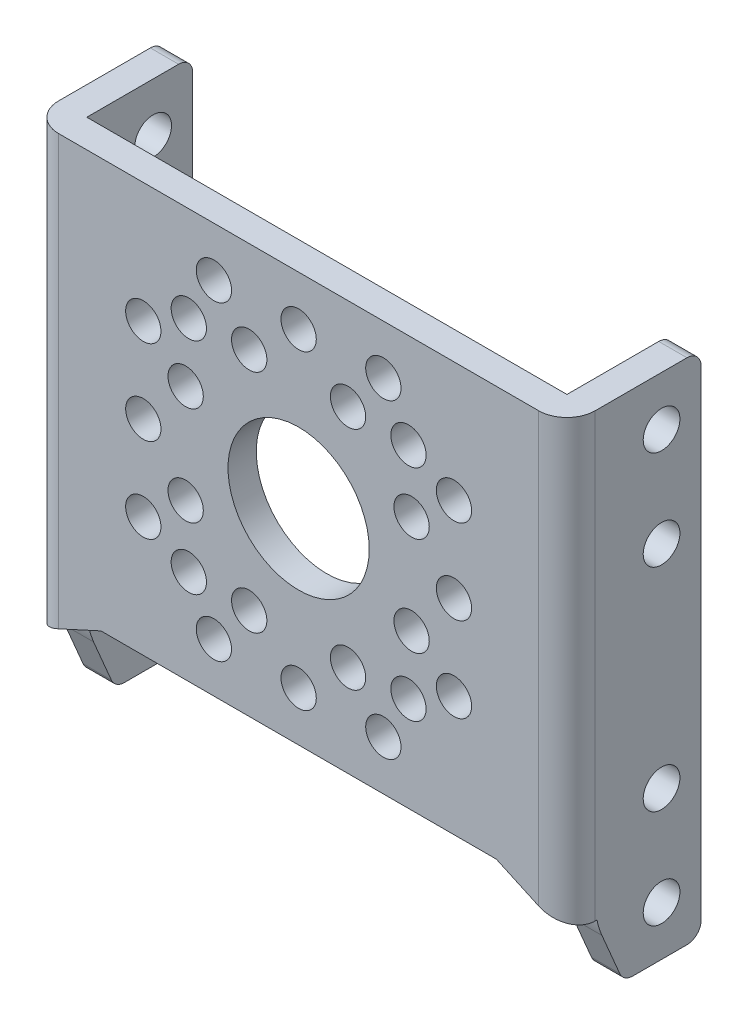
SolidWorks part; units mm, degrees
ref_plane "Front Plane" through (0, 0, 0) normal (0, 0, 1) x (1, 0, 0)
ref_plane "Top Plane" through (0, 0, 0) normal (0, 1, 0) x (1, 0, 0)
ref_plane "Right Plane" through (0, 0, 0) normal (1, 0, 0) x (0, 0, -1)
sketch "Sketch1" plane through (0, 0, 0) normal (0, 0, 1) x (1, 0, 0)
  line L0 (0, 14.5) -> (0, -14.5) construction
  line L1 (-19, 14.5) -> (19, 14.5)
  line L2 (-19, 14.5) -> (-19, -14.5)
  line L3 (-19, -14.5) -> (19, -14.5)
  line L4 (19, 14.5) -> (19, -14.5)
  line L5 (-19, 14.5) -> (19, -14.5) construction
  line L6 (-19, -14.5) -> (19, 14.5) construction
  circle A0 centre (0, 0) radius 11 construction
  circle A1 centre (0, -11) radius 1.25
  circle A2 centre (-7.7782, -7.7782) radius 1.25
  circle A3 centre (-11, 0) radius 1.25
  circle A4 centre (-7.7782, 7.7782) radius 1.25
  circle A5 centre (0, 11) radius 1.25
  circle A6 centre (7.7782, 7.7782) radius 1.25
  circle A7 centre (11, 0) radius 1.25
  circle A8 centre (7.7782, -7.7782) radius 1.25
  circle A9 centre (-6, -11) radius 1.25
  circle A10 centre (-11, 6) radius 1.25
  circle A11 centre (6, 11) radius 1.25
  circle A12 centre (11, -6) radius 1.25
  circle A13 centre (-11, -6) radius 1.25
  circle A14 centre (-6, 11) radius 1.25
  circle A15 centre (11, 6) radius 1.25
  circle A16 centre (6, -11) radius 1.25
  circle A17 centre (-3.5, -8) radius 1.25
  circle A18 centre (-8, 3.5) radius 1.25
  circle A19 centre (3.5, 8) radius 1.25
  circle A20 centre (8, -3.5) radius 1.25
  circle A21 centre (-8, -3.5) radius 1.25
  circle A22 centre (-3.5, 8) radius 1.25
  circle A23 centre (8, 3.5) radius 1.25
  circle A24 centre (3.5, -8) radius 1.25
  circle A27 centre (0, 0) radius 5
  point P28 (0, 0)
  point P37 (0, 0)
  point P46 (0, 0)
  point P55 (0, 0)
  point P64 (0, 0)
  dimension "D3" = 22
  dimension "D5" = 2.5
  dimension "D6" = 6
  dimension "D7" = 11
  dimension "D8" = 2.5
  dimension "D9" = 6
  dimension "D10" = 11
  dimension "D12" = 3.5
  dimension "D13" = 8
  dimension "D4" = 2.5
  dimension "D11" = 2.5
  dimension "D14" = 2.5
  dimension "D15" = 3.5
  dimension "D16" = 8
  dimension "D17" = 10
  dimension "D1" = 38
  dimension "D2" = 29
extrude "Boss-Extrude1" add sketch "Sketch1" along normal blind 2
sketch "Sketch2" plane through (-19, 0, 0) normal (-1, 0, 0) x (0, 0, 1)
  line L0 (2, 14.5) -> (-7.5, 14.5)
  line L1 (-7.5, 14.5) -> (-7.5, -21.5)
  line L2 (-7.5, -21.5) -> (-2, -21.5)
  line L3 (-2, -21.5) -> (0, -14.5)
  line L4 (0, -14.5) -> (2, -14.5)
  line L5 (2, -14.5) -> (2, 14.5)
  dimension "D1" = 9.5
  dimension "D2" = 36
  dimension "D3" = 5.5
extrude "Boss-Extrude2" add sketch "Sketch2" against normal blind 2
sketch "Sketch3" plane through (0, 0, 2) normal (0, 0, 1) x (1, 0, 0)
  line L0 (-19, -14.5) -> (-14, -14.5)
  line L1 (-19, -14.5) -> (19, -14.5) construction
  line L2 (-14, -14.5) -> (-19, -16.7913)
  line L3 (-19, -21.5) -> (-19, -14.5) construction
  line L4 (-19, -16.7913) -> (-19, -14.5)
  dimension "D1" = 5
  dimension "D2" = 5.5
extrude "Boss-Extrude3" add sketch "Sketch3" against normal blind 2
sketch "Sketch4" plane through (-19, 0, 0) normal (-1, 0, 0) x (0, 0, 1)
  line L0 (0, -14.5) -> (-2, -21.5)
  line L1 (-2, -21.5) -> (0, -16.7913)
  line L2 (0, -16.7913) -> (0, -14.5)
extrude "Boss-Extrude4" add sketch "Sketch4" against normal blind 2
fillet "Fillet4" radius 2 1 edges at (-19, -1.1456, 2)
fillet "Fillet5" radius 6 1 edges at (-18, -16.7913, 0)
fillet "Fillet6" radius 1 3 edges at (-18, 14.5, -7.5) (-18, -21.5, -7.5) (-18, -21.5, -2)
sketch "Sketch5" plane through (-19, 0, 0) normal (-1, 0, 0) x (0, 0, 1)
  line L0 (-4.7, 14.5) -> (-4.7, -21.5) construction
  line L1 (0, 14.5) -> (-6.5, 14.5) construction
  line L2 (-6.5, -21.5) -> (-2.6617, -21.5) construction
  line L3 (-7.5, 13.5) -> (-7.5, -20.5) construction
  line L4 (-7.5, -3.5) -> (-4.7, -3.5) construction
  line L5 (2, 14.5) -> (2, -15.8748) construction
  circle A0 centre (-4.7, 11) radius 1.3
  circle A1 centre (-4.7, -18) radius 1.3
  circle A2 centre (-4.7, 4) radius 1.3
  circle A3 centre (-4.7, -11) radius 1.3
  dimension "D2" = 14.5
  dimension "D4" = 7.5
  dimension "D6" = 2.6
  dimension "D3" = 14.5
  dimension "D5" = 7.5
  dimension "D7" = 6.7
extrude "Cut-Extrude1" cut sketch "Sketch5" against normal blind 2
mirror "Mirror3" about plane through (0, 0, 0) normal (1, 0, 0) of "Cut-Extrude1", "Fillet6", "Boss-Extrude4", "Boss-Extrude2", "Boss-Extrude3", "Fillet5"
fillet "Fillet7" radius 2 1 edges at (19, -1.1456, 2)
